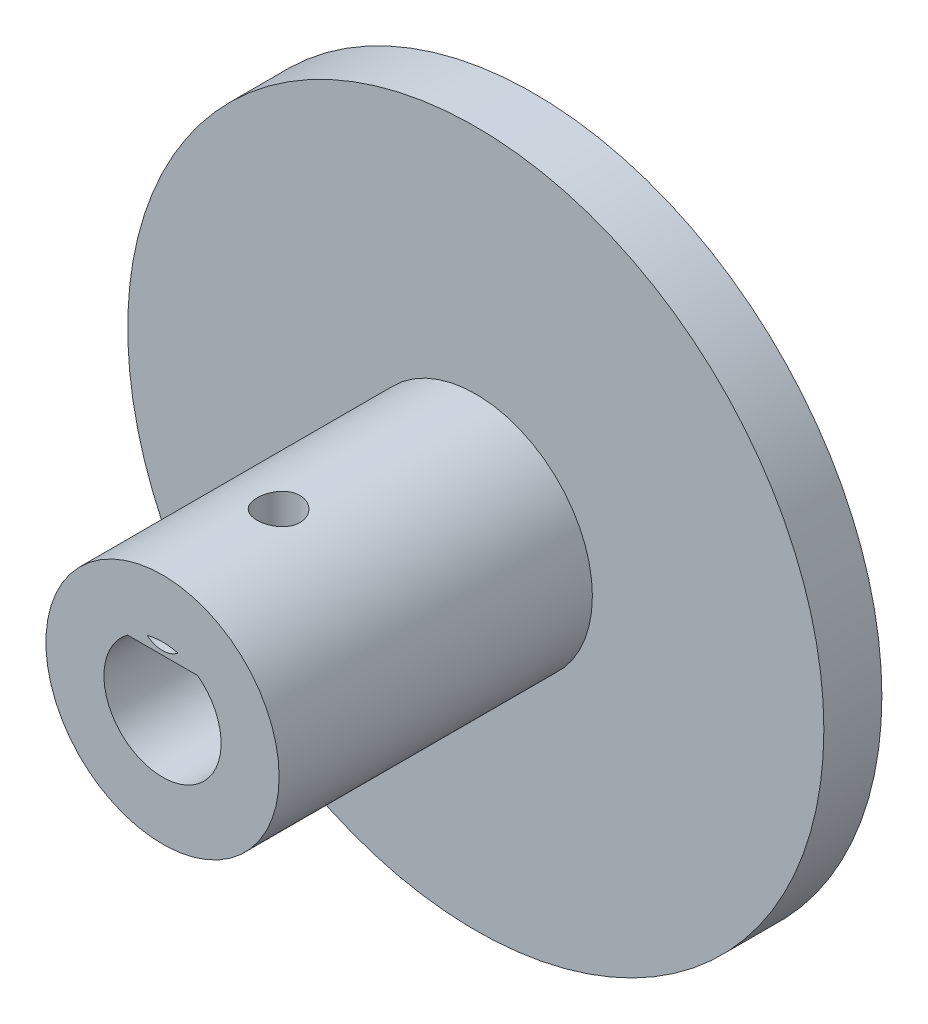
SolidWorks part; units mm, degrees
ref_plane "Front Plane" through (0, 0, 0) normal (0, 0, 1) x (1, 0, 0)
ref_plane "Top Plane" through (0, 0, 0) normal (0, 1, 0) x (1, 0, 0)
ref_plane "Right Plane" through (0, 0, 0) normal (1, 0, 0) x (0, 0, -1)
sketch "Sketch1" plane through (0, 0, 0) normal (0, 0, 1) x (1, 0, 0)
  line L1 (0, -6.5) -> (-6, 0) construction
  line L2 (0, -6.5) -> (6, 0) construction
  line L3 (6, 0) -> (0, 6.5) construction
  line L4 (-6, 0) -> (0, 6.5) construction
  line L5 (0, -6.5) -> (0, 6.5) construction
  line L6 (6, 0) -> (-6, 0) construction
  circle A0 centre (0, 0) radius 30
  circle A1 centre (0, 6.5) radius 2.1
  circle A15 centre (6, 0) radius 2.1
  circle A16 centre (0, -6.5) radius 2.1
  circle A17 centre (-6, 0) radius 2.1
  point P11 (0, 0.8421)
  point P12 (0, 2.394)
  point P13 (0, 0)
  point P14 (0, 0)
  dimension "D1" = 60
  dimension "D3" = 13
  dimension "D2" = 12
extrude "Boss-Extrude1" add sketch "Sketch1" along normal blind 5
sketch "Sketch2" plane through (0, 0, 5) normal (0, 0, 1) x (1, 0, 0)
  line L0 (-3.0166, 4.05) -> (3.0166, 4.05)
  line L1 (0, 4.05) -> (0, -5.05)
  circle A0 centre (0, 0) radius 5.05
  circle A1 centre (0, 0) radius 10.05
  circle M2 centre (0, 6.5) radius 2.1
  circle M26 centre (0, -6.5) radius 2.1
  circle M27 centre (6, 0) radius 2.1
  circle M28 centre (-6, 0) radius 2.1
  dimension "D1" = 10.1
  dimension "D2" = 9.1
  dimension "D3" = 5
extrude "Boss-Extrude2" add sketch "Sketch2" along normal blind 27 contours A1 A0 | L0 A0 | A0 M2 | A0 M27 | A0 M26 | A0 M28 region at (0, 4.3345, 5) region at (0, 6.6616, 5) region at (-6.3569, 0, 5) region at (6.3569, 0, 5) region at (0, -6.6616, 5) region at (-9.7657, 0, 5)
sketch "Sketch3" plane through (0, 4.05, 0) normal (0, -1, 0) x (-1, 0, 0)
  line L0 (-10.05, -32) -> (10.05, -32) construction
  circle A0 centre (0, -22) radius 1.85
  dimension "D2" = 3.7
  dimension "D1" = 10
extrude "Cut-Extrude1" cut sketch "Sketch3" against normal blind 20 and the other way blind 20
